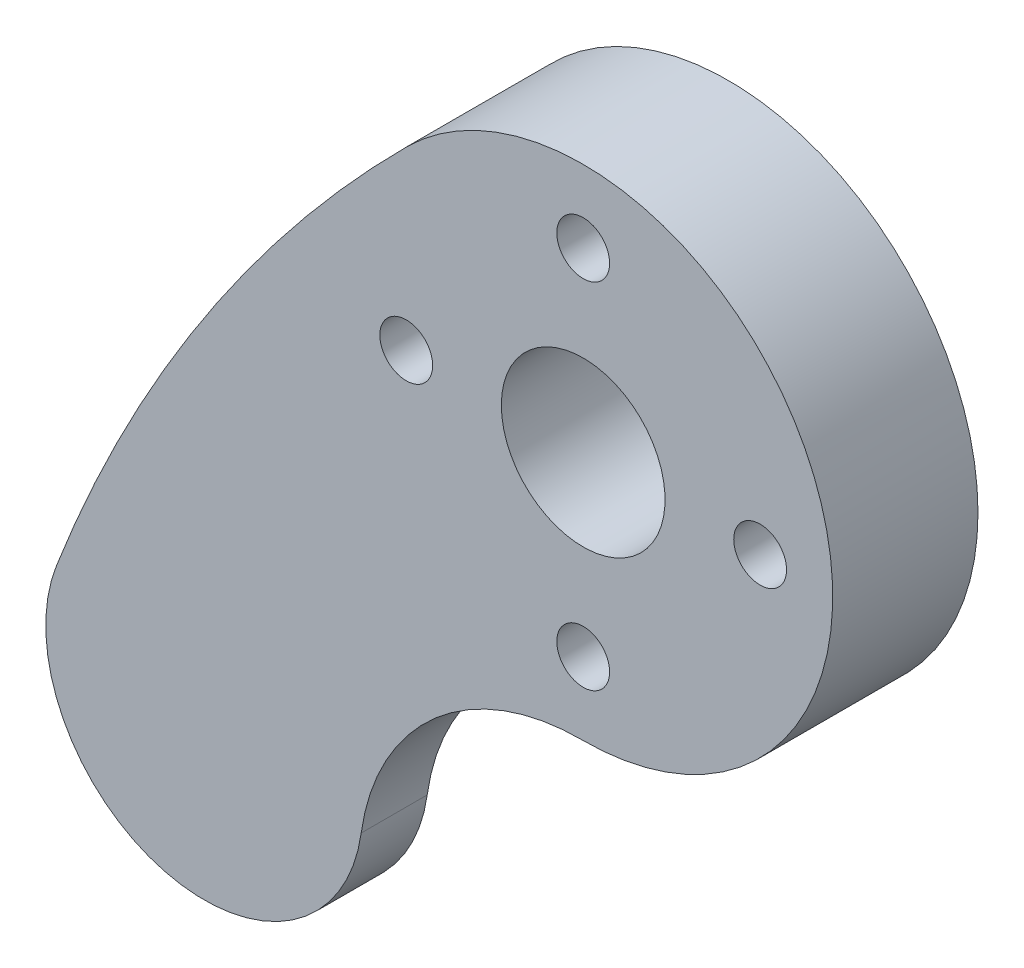
SolidWorks part; units mm, degrees
ref_plane "Front Plane" through (0, 0, 0) normal (0, 0, 1) x (1, 0, 0)
ref_plane "Top Plane" through (0, 0, 0) normal (0, 1, 0) x (1, 0, 0)
ref_plane "Right Plane" through (0, 0, 0) normal (1, 0, 0) x (0, 0, -1)
sketch "Sketch1" plane through (0, 0, 0) normal (0, 0, 1) x (1, 0, 0)
  line L0 (70.1254, 27.305) -> (58.42, 27.305) construction
  line L1 (58.42, 27.305) -> (58.42, 0) construction
  line L2 (58.42, 0) -> (99.06, 0) construction
  line L3 (99.06, 0) -> (99.06, 31.75) construction
  line L4 (99.06, 31.75) -> (73.66, 31.75) construction
  line L5 (73.66, 31.75) -> (73.66, 28.6195) construction
  line L6 (78.6801, 26.924) -> (87.4395, 26.924) construction
  line L7 (87.4395, 26.924) -> (87.4395, 24.13) construction
  line L8 (87.4395, 24.13) -> (80.9328, 22.479) construction
  line L9 (70.1254, 27.305) -> (58.42, 27.305)
  line L10 (58.42, 27.305) -> (58.42, 0)
  line L11 (58.42, 0) -> (99.06, 0)
  line L12 (99.06, 0) -> (99.06, 31.75)
  line L13 (99.06, 31.75) -> (73.66, 31.75)
  line L14 (73.66, 31.75) -> (73.66, 28.6195)
  line L15 (78.6801, 26.924) -> (87.4395, 26.924)
  line L16 (87.4395, 26.924) -> (87.4395, 24.13)
  line L17 (87.4395, 24.13) -> (80.9328, 22.479)
  line L18 (80.8812, 20.7957) -> (87.5941, 20.7957)
  line L19 (87.5941, 20.7957) -> (88.2812, 23.5039)
  line L20 (88.2812, 23.5039) -> (79.7909, 25.6582)
  line L21 (80.9328, 22.479) -> (87.4395, 26.924) construction
  line L22 (88.2812, 23.5039) -> (80.8812, 20.7957) construction
  line L23 (87.5941, 20.7957) -> (79.7909, 25.6582) construction
  line L24 (78.6801, 26.924) -> (87.4395, 24.13) construction
  line L25 (81.3178, 26.0826) -> (111.6739, 61.618) construction
  arc A0 (78.6801, 26.924) -> (73.66, 28.6195) centre (74.168, 21.844) ccw construction
  arc A1 (70.1254, 27.305) -> (80.9328, 22.479) centre (74.168, 21.844) ccw construction
  circle A2 centre (104.4893, 52.0065) radius 12 construction
  arc A3 (78.6801, 26.924) -> (73.66, 28.6195) centre (74.168, 21.844) ccw
  arc A4 (70.1254, 27.305) -> (80.9328, 22.479) centre (74.168, 21.844) ccw
  circle A5 centre (104.4893, 52.0065) radius 12
  circle A6 centre (56.226, 91.417) radius 74.31
  circle A7 centre (86.2672, 31.8764) radius 7.62
  circle A8 centre (148.4954, 7.8931) radius 74.31
  dimension "D2" = 15.24
  dimension "D1" = 46.736
extrude "Boss-Extrude1" add sketch "Sketch1" along normal blind 3.175 contours L13 A7 | L13 A7 L15 L16 | L15 A7 L16 | A7 A6 L12 L13 | A5 A8 A7 L13 L12 A6 | A5 region at (94.0508, 41.3164, 0) region at (104.4893, 52.0065, 0) region at (95.3834, 29.7296, 0) region at (86.5606, 29.0842, 0) region at (84.6642, 25.7868, 0) region at (86.2672, 35.0423, 0)
sketch "Sketch2" plane through (0, 0, 0) normal (0, 0, -1) x (-1, 0, 0)
  circle A0 centre (-104.4893, 52.0065) radius 12
extrude "Boss-Extrude2" add sketch "Sketch2" along normal blind 3.81
sketch "Sketch3" plane through (0, 0, -3.81) normal (0, 0, -1) x (-1, 0, 0)
  circle A1 centre (-104.4893, 52.0065) radius 12
  circle A2 centre (-104.4893, 52.0065) radius 12
  circle A4 centre (-104.4893, 52.0065) radius 3.937
  dimension "D2" = 7.874
  dimension "D1" = 0
extrude "Cut-Extrude1" cut sketch "Sketch3" against normal through all contours A4
sketch "Sketch4" plane through (0, 0, -3.81) normal (0, 0, -1) x (-1, 0, 0)
  line L0 (-104.4893, 60.5155) -> (-104.4893, 52.0065) construction
  line L1 (-104.4893, 52.0065) -> (-104.4893, 43.4975) construction
  line L2 (-104.4893, 52.0065) -> (-95.9803, 52.0065) construction
  line L3 (-104.4893, 52.0065) -> (-112.9983, 52.0065) construction
  circle A1 centre (-104.4893, 52.0065) radius 12
  circle A2 centre (-104.4893, 52.0065) radius 12
  circle A5 centre (-104.4893, 52.0065) radius 8.509 construction
  circle A6 centre (-95.9803, 52.0065) radius 1.27
  circle A7 centre (-112.9983, 52.0065) radius 1.27
  circle A8 centre (-104.4893, 43.4975) radius 1.27
  circle A9 centre (-104.4893, 60.5155) radius 1.27
  dimension "D2" = 17.018
  dimension "D3" = 2.54
  dimension "D1" = 0
extrude "Cut-Extrude2" cut sketch "Sketch4" against normal through all contours A7 | A6 | A9 | A8 region at (95.9803, 52.0065, -3.81) region at (112.9983, 52.0065, -3.81)
sketch "Sketch5" plane through (0, 0, 0) normal (0, 0, -1) x (-1, 0, 0)
  arc A0 (-113.7841, 44.4166) -> (-96.0143, 60.5021) centre (-104.4893, 52.0065) ccw construction
  arc A1 (-113.7841, 44.4166) -> (-89.6997, 25.0733) centre (-56.226, 91.417) ccw construction
  arc A2 (-89.6997, 25.0733) -> (-79.157, 34.6168) centre (-86.2672, 31.8764) ccw construction
  arc A3 (-79.157, 34.6168) -> (-96.0143, 60.5021) centre (-148.4954, 7.8931) ccw construction
  circle A4 centre (-104.4893, 52.0065) radius 12 construction
  arc A5 (-113.7841, 44.4166) -> (-96.0143, 60.5021) centre (-104.4893, 52.0065) ccw
  arc A6 (-113.7841, 44.4166) -> (-89.6997, 25.0733) centre (-56.226, 91.417) ccw
  arc A7 (-89.6997, 25.0733) -> (-79.157, 34.6168) centre (-86.2672, 31.8764) ccw
  arc A8 (-79.157, 34.6168) -> (-96.0143, 60.5021) centre (-148.4954, 7.8931) ccw
  circle A9 centre (-104.4893, 52.0065) radius 12
  circle A10 centre (-86.2672, 31.8764) radius 7.62
  circle A11 centre (-104.4893, 52.0065) radius 12
  arc A12 (-93.8135, 30.8191) -> (-104.4305, 40.0066) centre (-104.3783, 29.3388) ccw
  arc M2 (-113.7841, 44.4166) -> (-89.6997, 25.0733) centre (-56.226, 91.417) ccw
  dimension "D1" = 10.668
extrude "Cut-Extrude3" cut sketch "Sketch5" against normal through all contours A10 A12 A11 M2 region at (100.4293, 35.0094, 0)
